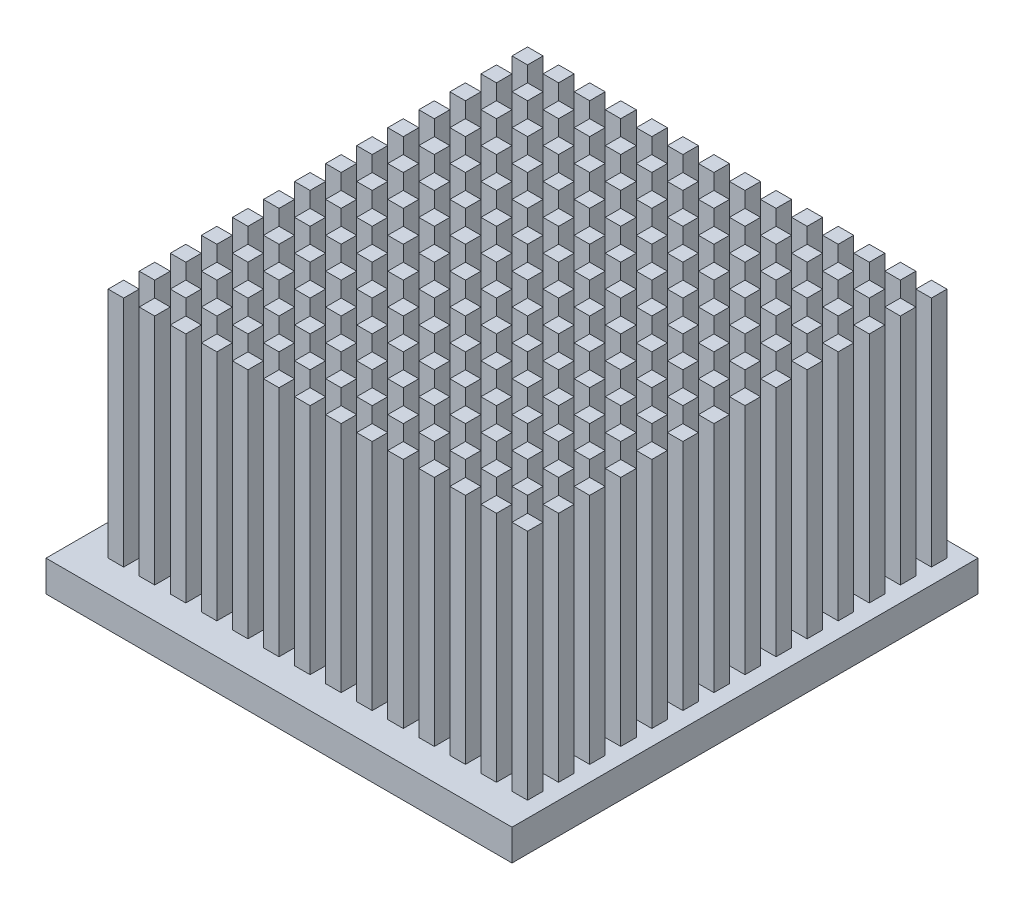
SolidWorks part; units mm, degrees
ref_plane "Front Plane" through (0, 0, 0) normal (0, 0, 1) x (1, 0, 0)
ref_plane "Top Plane" through (0, 0, 0) normal (0, 1, 0) x (1, 0, 0)
ref_plane "Right Plane" through (0, 0, 0) normal (1, 0, 0) x (0, 0, -1)
sketch "Sketch1" plane through (0, 0, 0) normal (0, 0, 1) x (1, 0, 0)
  line L1 (-75, -5) -> (75, -5)
  line L2 (-75, -5) -> (-75, 5)
  line L3 (-75, 5) -> (75, 5)
  line L4 (75, -5) -> (75, 5)
  line L5 (-75, -5) -> (75, 5) construction
  line L6 (-75, 5) -> (75, -5) construction
  point P0 (0, 0)
  dimension "D1" = 150
  dimension "D2" = 10
extrude "Boss-Extrude1" add sketch "Sketch1" along normal blind 75 and the other way blind 75
sketch "Sketch2" plane through (0, 5, 0) normal (0, 1, 0) x (1, 0, 0)
  line L1 (65, 70) -> (70, 70)
  line L2 (65, 70) -> (65, 65)
  line L3 (65, 65) -> (70, 65)
  line L4 (70, 70) -> (70, 65)
  line L5 (65, 70) -> (70, 65) construction
  line L6 (65, 65) -> (70, 70) construction
  point P0 (67.5, 67.5)
  dimension "D1" = 5
  dimension "D2" = 5
  dimension "D3" = 5
  dimension "D4" = 5
extrude "Boss-Extrude2" add sketch "Sketch2" along normal blind 75
pattern_linear "LPattern1" count 14 spacing 10 along (0, 0, 1) count 14 spacing 10 along (-1, 0, 0) of "Boss-Extrude2"
